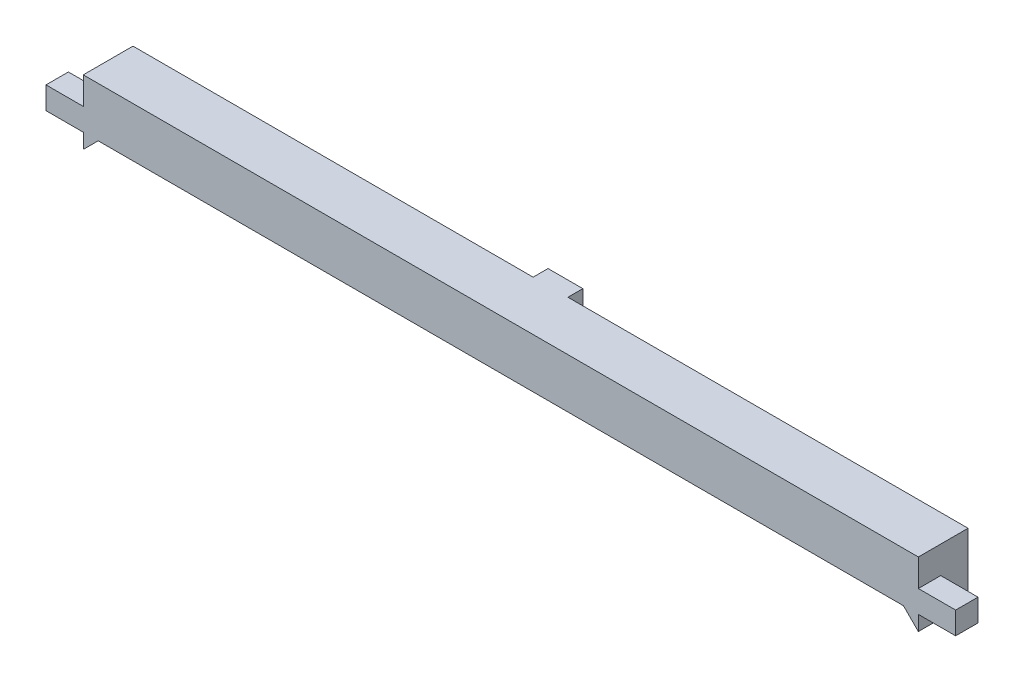
SolidWorks part; units mm, degrees
ref_plane "정면" through (0, 0, 0) normal (0, 0, 1) x (1, 0, 0)
ref_plane "윗면" through (0, 0, 0) normal (0, 1, 0) x (1, 0, 0)
ref_plane "우측면" through (0, 0, 0) normal (1, 0, 0) x (0, 0, -1)
sketch "스케치1" plane through (0, 0, 0) normal (0, 0, 1) x (1, 0, 0)
  line L0 (-318.5049, 0) -> (318.5049, 0) construction
  line L1 (0, 0) -> (0, -258.8265) construction
  line L2 (-168, 0) -> (168, 0)
  line L3 (-168, -20) -> (168, -20)
  line L4 (168, -20) -> (168, 0) construction
  line L5 (168, -20) -> (168, -340)
  line L6 (172, -340) -> (172, 0)
  line L7 (168, 0) -> (183, 0)
  line L8 (183, 0) -> (183, -340)
  line L9 (183, -340) -> (168, -340)
  line L10 (-168, -20) -> (-168, 0) construction
  line L11 (-183, -340) -> (-168, -340)
  line L12 (-183, 0) -> (-183, -340)
  line L13 (-168, 0) -> (-183, 0)
  line L14 (-172, -340) -> (-172, 0)
  line L15 (-168, -20) -> (-168, -340)
  line L16 (168, -20) -> (168, 0)
  line L17 (-168, -20) -> (-168, 0)
  point P14 (0, -20)
  dimension "D1" = 168
  dimension "D2" = 20
  dimension "D3" = 4
  dimension "D4" = 340
  dimension "D5" = 15
extrude "보스-돌출1" add sketch "스케치1" along normal blind 26 contours L3 L5 L9 L8 L7 L2 L13 L12 L11 L15
extrude "보스-돌출2" add sketch "스케치1<4>" against normal blind 19 contours L16 L5 L9 L6 L7 | L15 L17 L13 L14 L11 region at (-170, -170, 0) region at (170, -170, 0)
sketch "스케치1<4>" plane through (0, 0, 0) normal (0, 0, 1) x (1, 0, 0) same geometry as "스케치1"
fillet "필렛1" radius 10 4 edges at (-170, 0, -19) (170, 0, -19) (170, -340, -19) (-170, -340, -19)
sketch "스케치2" plane through (172, 0, 0) normal (1, 0, 0) x (0, 0, -1)
  line L0 (14, -340) -> (14, 0)
  line L1 (12, 0) -> (12, -340)
  line L4 (19, -330) -> (19, -10)
  line L5 (9, 0) -> (0, 0)
  line L6 (0, 0) -> (0, -340)
  line L7 (0, -340) -> (9, -340)
  line L8 (19, -330) -> (19, -10)
  line L9 (9, 0) -> (0, 0)
  line L10 (0, 0) -> (0, -340)
  line L11 (0, -340) -> (9, -340)
  arc A2 (19, -10) -> (9, 0) centre (9, -10) ccw
  arc A3 (9, -340) -> (19, -330) centre (9, -330) ccw
  arc A4 (19, -10) -> (9, 0) centre (9, -10) ccw
  arc A5 (9, -340) -> (19, -330) centre (9, -330) ccw
  dimension "D2" = 5
  dimension "D3" = 2
  dimension "D1" = 0
sketch "스케치3" plane through (168, 0, 0) normal (-1, 0, 0) x (0, 0, 1)
  line L0 (-12, 0) -> (-12, -340) construction
  line L1 (-14, -340) -> (-14, 0) construction
  line L2 (-12, 0) -> (-12, -340)
  line L3 (-14, -340) -> (-14, 0)
  line L4 (-19, -10) -> (-19, -330)
  line L5 (0, 0) -> (-9, 0)
  line L6 (0, -340) -> (0, 0)
  line L7 (-9, -340) -> (0, -340)
  line L8 (-19, -10) -> (-19, -330)
  line L9 (0, 0) -> (-9, 0)
  line L10 (0, -340) -> (0, 0)
  line L11 (-9, -340) -> (0, -340)
  arc A2 (-9, 0) -> (-19, -10) centre (-9, -10) ccw
  arc A3 (-19, -330) -> (-9, -340) centre (-9, -330) ccw
  arc A4 (-9, 0) -> (-19, -10) centre (-9, -10) ccw
  arc A5 (-19, -330) -> (-9, -340) centre (-9, -330) ccw
  arc M8 (-9, 0) -> (-19, -10) centre (-9, -10) ccw
  arc M10 (-19, -330) -> (-9, -340) centre (-9, -330) ccw
  dimension "D1" = 0
extrude "보스-돌출3" add sketch "스케치3" along normal blind 2 contours L3 L2 M10 M8 region at (168, -170, -12.9991)
mirror "대칭 복사1" about plane through (0, 0, 0) normal (1, 0, 0) of "보스-돌출3"
sketch "스케치5" plane through (0, 0, 0) normal (0, 1, 0) x (1, 0, 0)
  line L0 (-7, 0) -> (-7, -26)
  line L1 (7, 0) -> (7, -26)
  line L2 (-168, 0) -> (-168, -6)
  line L3 (-168, -6) -> (-7, -6)
  line L4 (7, -6) -> (168, -6)
  line L5 (168, -6) -> (168, 0)
  line L12 (-168, 0) -> (-168, 9)
  line L13 (-168, 9) -> (-172, 9)
  line L14 (-172, 9) -> (-172, 0)
  line L15 (-172, 0) -> (-183, 0)
  line L16 (-183, 0) -> (-183, -26)
  line L17 (-183, -26) -> (183, -26)
  line L18 (183, -26) -> (183, 0)
  line L19 (183, 0) -> (172, 0)
  line L20 (172, 0) -> (172, 9)
  line L21 (172, 9) -> (168, 9)
  line L22 (168, 9) -> (168, 0)
  line L23 (168, 0) -> (-168, 0)
  line L24 (-168, 0) -> (-168, 9)
  line L25 (-168, 9) -> (-172, 9)
  line L26 (-172, 9) -> (-172, 0)
  line L27 (-172, 0) -> (-183, 0)
  line L28 (-183, 0) -> (-183, -26)
  line L29 (-183, -26) -> (183, -26)
  line L30 (183, -26) -> (183, 0)
  line L31 (183, 0) -> (172, 0)
  line L32 (172, 0) -> (172, 9)
  line L33 (172, 9) -> (168, 9)
  line L34 (168, 9) -> (168, 0)
  line L35 (168, 0) -> (-168, 0)
  line M27 (168, 0) -> (-168, 0)
  dimension "D2" = 7
  dimension "D3" = 7
  dimension "D4" = 6
  dimension "D1" = 0
extrude "컷-돌출1" cut sketch "스케치5" against normal blind 52 contours L2 L3 L0 M27 | L4 L5 L1 M27 region at (-87.5, 0, 3) region at (87.5, 0, 3)
sketch "스케치7" plane through (168, 0, 0) normal (-1, 0, 0) x (0, 0, 1)
  line L0 (26, 0) -> (6, 0)
  line L1 (-9, 0) -> (6, 0)
  line L2 (-14, -338.6603) -> (-14, -1.3397)
  line L3 (-19, -10) -> (-19, -330)
  line L4 (-14, -338.6603) -> (-14, -1.3397)
  line L5 (-19, -10) -> (-19, -330)
  line L6 (26, -20) -> (6, -20)
  line L7 (6, -20) -> (6, 0)
  line L8 (6, 0) -> (-9, 0)
  line L9 (-12, -0.4606) -> (-12, -339.5394)
  line L10 (-9, -340) -> (26, -340)
  line L11 (26, -340) -> (26, -20)
  line L12 (26, -20) -> (6, -20)
  line L13 (6, -20) -> (6, 0)
  line L14 (6, 0) -> (-9, 0)
  line L15 (-12, -0.4606) -> (-12, -339.5394)
  line L16 (-9, -340) -> (26, -340)
  line L17 (26, -340) -> (26, -20)
  line L18 (-9, 0) -> (6, 0)
  line L19 (26, 0) -> (6, 0)
  line L20 (26, -20) -> (26, -340)
  line L21 (26, -20) -> (26, 0)
  line L22 (26, -20) -> (26, 0)
  line L23 (26, -20) -> (26, -340)
  arc A1 (-19, -330) -> (-14, -338.6603) centre (-9, -330) ccw
  arc A2 (-9, 0) -> (-12, -0.4606) centre (-9, -10) ccw
  arc A3 (-12, -339.5394) -> (-9, -340) centre (-9, -330) ccw
  arc A4 (-9, 0) -> (-12, -0.4606) centre (-9, -10) ccw
  arc A5 (-12, -339.5394) -> (-9, -340) centre (-9, -330) ccw
  arc A6 (-19, -330) -> (-14, -338.6603) centre (-9, -330) ccw
  arc A7 (-14, -1.3397) -> (-19, -10) centre (-9, -10) ccw
  arc A8 (-19, -330) -> (-14, -338.6603) centre (-9, -330) ccw
  arc A9 (-14, -1.3397) -> (-19, -10) centre (-9, -10) ccw
  arc A10 (-14, -338.6603) -> (-12, -339.5394) centre (-9, -330) ccw
  arc A11 (-12, -339.5394) -> (-9, -340) centre (-9, -330) ccw
  arc A12 (-12, -339.5394) -> (-9, -340) centre (-9, -330) ccw
  arc A13 (-14, -338.6603) -> (-12, -339.5394) centre (-9, -330) ccw
  arc A14 (-19, -330) -> (-14, -338.6603) centre (-9, -330) ccw
  arc A15 (-9, 0) -> (-12, -0.4606) centre (-9, -10) ccw
  arc A16 (-12, -0.4606) -> (-14, -1.3397) centre (-9, -10) ccw
  arc A17 (-14, -1.3397) -> (-19, -10) centre (-9, -10) ccw
  arc A18 (-14, -1.3397) -> (-19, -10) centre (-9, -10) ccw
  arc A19 (-12, -0.4606) -> (-14, -1.3397) centre (-9, -10) ccw
  arc A20 (-9, 0) -> (-12, -0.4606) centre (-9, -10) ccw
  line M13 (26, -20) -> (6, -20)
  line M14 (6, -20) -> (6, 0)
  line M15 (6, 0) -> (-9, 0)
  arc M16 (-9, 0) -> (-12, -0.4606) centre (-9, -10) ccw
  line M17 (-12, -0.4606) -> (-12, -339.5394)
  arc M18 (-12, -339.5394) -> (-9, -340) centre (-9, -330) ccw
  line M19 (-9, -340) -> (26, -340)
  line M20 (26, -340) -> (26, -20)
  dimension "D1" = 0
  dimension "D2" = 0
extrude "컷-돌출2" cut sketch "스케치7" against normal blind 72 contours M20 M13 M14 M15 M16 M17 M18 M19 | L4 A9 L5 A8 | A19 L4 A13 M17 | L22 L19 M13 M14 region at (168, -10, 16) region at (168, -175.1122, 6.7138) region at (168, -170, -12.9991) region at (168, -170, -16.4834)
sketch "스케치8" plane through (-168, 0, 0) normal (1, 0, 0) x (0, 0, -1)
  line L6 (-6, 0) -> (-6, -20)
  line L7 (-6, -20) -> (-26, -20)
  line L8 (-26, -20) -> (-26, -340)
  line L9 (-26, -340) -> (9, -340)
  line L10 (12, -339.5394) -> (12, -0.4606)
  line L11 (9, 0) -> (-6, 0)
  line L12 (-6, 0) -> (-6, -20)
  line L13 (-6, -20) -> (-26, -20)
  line L14 (-26, -20) -> (-26, -340)
  line L15 (-26, -340) -> (9, -340)
  line L16 (12, -339.5394) -> (12, -0.4606)
  line L17 (9, 0) -> (-6, 0)
  line L18 (9, 0) -> (-6, 0)
  line L19 (-6, 0) -> (-26, 0)
  line L20 (-6, 0) -> (-26, 0)
  line L21 (9, 0) -> (-6, 0)
  line L22 (-26, 0) -> (-26, -20)
  line L23 (-26, -20) -> (-26, -340)
  line L24 (-26, -20) -> (-26, -340)
  line L25 (-26, 0) -> (-26, -20)
  arc A2 (9, -340) -> (12, -339.5394) centre (9, -330) ccw
  arc A3 (12, -0.4606) -> (9, 0) centre (9, -10) ccw
  arc A4 (9, -340) -> (12, -339.5394) centre (9, -330) ccw
  arc A5 (12, -0.4606) -> (9, 0) centre (9, -10) ccw
  line M9 (-6, 0) -> (-6, -20)
  line M10 (-6, -20) -> (-26, -20)
  line M11 (-26, -20) -> (-26, -340)
  line M12 (-26, -340) -> (9, -340)
  arc M13 (9, -340) -> (12, -339.5394) centre (9, -330) ccw
  line M14 (12, -339.5394) -> (12, -0.4606)
  arc M15 (12, -0.4606) -> (9, 0) centre (9, -10) ccw
  line M16 (9, 0) -> (-6, 0)
  dimension "D1" = 0
extrude "컷-돌출3" cut sketch "스케치8" against normal blind 72 contours M16 M9 M10 M11 M12 M13 M14 M15 | L20 L25 M10 M9 region at (-168, -175.1122, 6.7138) region at (-168, -10, 16)
extrude "컷-돌출4" cut sketch "스케치7<3>" along normal blind 362 contours L4 A9 L5 A8 | A19 L4 A13 M17 region at (168, -170, -12.9991) region at (168, -170, -16.4834)
sketch "스케치7<3>" plane through (168, 0, 0) normal (-1, 0, 0) x (0, 0, 1) same geometry as "스케치7"
sketch "스케치9" plane through (168, 0, 0) normal (1, 0, 0) x (0, 0, -1)
  line L0 (9, -340) -> (-26, -340) construction
  line L1 (-26, -340) -> (-26, -20) construction
  line L2 (-26, -20) -> (-26, -340) construction
  line L3 (12, -0.4606) -> (12, -339.5394) construction
  line L4 (-6, -20) -> (-6, 0)
  line L5 (-6, 0) -> (-26, 0)
  line L6 (-26, 0) -> (-26, -20)
  line L7 (-26, -20) -> (-6, -20)
  line L8 (-6, -20) -> (-6, 0)
  line L9 (-6, 0) -> (-26, 0)
  line L10 (-26, 0) -> (-26, -20)
  line L11 (-26, -20) -> (-6, -20)
  line L12 (-6, 0) -> (9, 0) construction
  line L13 (9, 0) -> (-6, 0) construction
  line L14 (-26, -20) -> (-6, -20) construction
  line L15 (-6, -20) -> (-6, 0) construction
  line L16 (-26, 0) -> (-6, 0) construction
  line L17 (-26, -20) -> (-26, 0) construction
  line L18 (19, -10) -> (19, -330) construction
  line L19 (14, -338.6603) -> (14, -1.3397) construction
  line L20 (9, -340) -> (-26, -340)
  line L21 (-26, -340) -> (-26, -20)
  line L22 (-26, -20) -> (-26, -340)
  line L23 (12, -0.4606) -> (12, -339.5394)
  line L24 (-6, 0) -> (9, 0)
  line L25 (9, 0) -> (-6, 0)
  line L26 (-26, -20) -> (-6, -20)
  line L27 (-6, -20) -> (-6, 0)
  line L28 (-26, 0) -> (-6, 0)
  line L29 (-26, -20) -> (-26, 0)
  line L30 (19, -10) -> (19, -330)
  line L31 (14, -338.6603) -> (14, -1.3397)
  line L32 (-26, -10) -> (-16, -10)
  line L33 (-16, -10) -> (-16, -20)
  line L34 (-26, -11) -> (-17, -11)
  line L35 (-17, -11) -> (-17, -20)
  arc A0 (9, -340) -> (12, -339.5394) centre (9, -330) ccw construction
  arc A1 (9, -340) -> (12, -339.5394) centre (9, -330) ccw construction
  arc A2 (12, -339.5394) -> (14, -338.6603) centre (9, -330) ccw construction
  arc A3 (12, -0.4606) -> (9, 0) centre (9, -10) ccw construction
  arc A4 (14, -1.3397) -> (12, -0.4606) centre (9, -10) ccw construction
  arc A5 (12, -0.4606) -> (9, 0) centre (9, -10) ccw construction
  arc A6 (14, -338.6603) -> (19, -330) centre (9, -330) ccw construction
  arc A7 (14, -338.6603) -> (19, -330) centre (9, -330) ccw construction
  arc A8 (19, -10) -> (14, -1.3397) centre (9, -10) ccw construction
  arc A9 (19, -10) -> (14, -1.3397) centre (9, -10) ccw construction
  arc A10 (9, -340) -> (12, -339.5394) centre (9, -330) ccw
  arc A11 (9, -340) -> (12, -339.5394) centre (9, -330) ccw
  arc A12 (12, -339.5394) -> (14, -338.6603) centre (9, -330) ccw
  arc A13 (12, -0.4606) -> (9, 0) centre (9, -10) ccw
  arc A14 (14, -1.3397) -> (12, -0.4606) centre (9, -10) ccw
  arc A15 (12, -0.4606) -> (9, 0) centre (9, -10) ccw
  arc A16 (14, -338.6603) -> (19, -330) centre (9, -330) ccw
  arc A17 (14, -338.6603) -> (19, -330) centre (9, -330) ccw
  arc A18 (19, -10) -> (14, -1.3397) centre (9, -10) ccw
  arc A19 (19, -10) -> (14, -1.3397) centre (9, -10) ccw
  line M9 (-26, 0) -> (-26, -20)
  line M10 (-26, -20) -> (-6, -20)
  dimension "D2" = 10
  dimension "D3" = 10
  dimension "D1" = 0
  dimension "D4" = 1
extrude "보스-돌출4" add sketch "스케치9" along normal blind 15 contours L35 L34 M9 M10 region at (168, -15.5, 21.5)
mirror "대칭 복사2" about plane through (0, 0, 0) normal (1, 0, 0) of "보스-돌출4"
sketch "스케치10" plane through (0, 0, 26) normal (0, 0, 1) x (1, 0, 0)
  line L8 (-168, 0) -> (-168, -11)
  line L9 (-168, -11) -> (-183, -11)
  line L10 (-183, -11) -> (-183, -20)
  line L11 (-183, -20) -> (183, -20)
  line L12 (183, -20) -> (183, -11)
  line L13 (183, -11) -> (168, -11)
  line L14 (168, -11) -> (168, 0)
  line L15 (168, 0) -> (-168, 0)
  line L16 (-168, 0) -> (-168, -11)
  line L17 (-168, -11) -> (-183, -11)
  line L18 (-183, -11) -> (-183, -20)
  line L19 (-183, -20) -> (183, -20)
  line L20 (183, -20) -> (183, -11)
  line L21 (183, -11) -> (168, -11)
  line L22 (168, -11) -> (168, 0)
  line L23 (168, 0) -> (-168, 0)
  line L24 (-183, -20) -> (183, -20)
  line L25 (-183, -20) -> (183, -20)
  line L26 (168, -11) -> (168, 0)
  line L27 (168, -11) -> (168, 0)
  line L28 (168, -11) -> (168, -36.4678) construction
  line L29 (168, -20) -> (168, -26)
  line L30 (168, -26) -> (162, -20)
  line L31 (0, 0) -> (0, -20) construction
  dimension "D2" = 6
  dimension "D3" = 6
  dimension "D1" = 0
extrude "보스-돌출5" add sketch "스케치10" against normal blind 20 contours L30 L29 L25 region at (166, -22, 26)
mirror "대칭 복사3" about plane through (0, 0, 0) normal (1, 0, 0) of "보스-돌출5"
sketch "스케치11" plane through (0, 0, 0) normal (0, 1, 0) x (1, 0, 0)
  line L0 (0, -26) -> (0, 64.4586) construction
  line L1 (168, -26) -> (-168, -26) construction
  line L2 (7, -6) -> (168, -6)
  line L3 (7, -6) -> (168, -6)
  line L4 (-168, -6) -> (-7, -6)
  line L5 (-168, -6) -> (-7, -6)
  line L6 (168, -26) -> (-168, -26)
  line L7 (168, -26) -> (-168, -26)
  line L8 (0, -26) -> (0, -21.153)
  line L9 (-1.1414, -20.1631) -> (-5.8586, -20.8369)
  line L10 (-7, -19.847) -> (-7, -14.153)
  line L11 (-5.8586, -13.1631) -> (-1.1414, -13.8369)
  line L12 (0, -12.847) -> (0, -7)
  line L13 (-7, 0) -> (-7, -6) construction
  line L14 (-7, -6) -> (-1, -6)
  line L15 (-168, -6) -> (-168, -26)
  line L16 (-168, -6) -> (-168, -26)
  line L17 (-0.5, -26) -> (-0.5, -21.153)
  line L18 (-1.0707, -20.658) -> (-5.7879, -21.3319)
  line L19 (-7.5, -19.847) -> (-7.5, -14.153)
  line L20 (-5.7879, -12.6681) -> (-1.0707, -13.342)
  line L21 (-168, -26) -> (-168, -17)
  line L22 (-168, -17) -> (-183, -17)
  line L23 (-183, -17) -> (-183, -26)
  line L24 (-183, -26) -> (-168, -26)
  line L25 (-168, -26) -> (-168, -17)
  line L26 (-168, -17) -> (-183, -17)
  line L27 (-183, -17) -> (-183, -26)
  line L28 (-183, -26) -> (-168, -26)
  line L29 (-0.5, -12.847) -> (-0.5, -7)
  line L30 (-7, -6.5) -> (-1, -6.5)
  line L31 (-7, -6.5) -> (-7, -6)
  line L32 (168, -6) -> (203.629, -6)
  line L33 (203.629, -6) -> (203.629, -26)
  line L34 (203.629, -26) -> (168, -26)
  line L35 (-7, 0) -> (7, 0)
  line L36 (-7, 0) -> (7, 0)
  line L37 (-7, 0) -> (-7, -6)
  line L38 (-7, 0) -> (-7, -6)
  line L39 (7, 0) -> (7, -6)
  line L40 (7, 0) -> (7, -6)
  line L41 (0, -21.153) -> (0, -12.847)
  arc A0 (0, -21.153) -> (-1.1414, -20.1631) centre (-1, -21.153) ccw
  arc A1 (-1.1414, -13.8369) -> (0, -12.847) centre (-1, -12.847) ccw
  arc A2 (-7, -14.153) -> (-5.8586, -13.1631) centre (-6, -14.153) cw
  arc A3 (-7, -19.847) -> (-5.8586, -20.8369) centre (-6, -19.847) ccw
  arc A4 (0, -7) -> (-1, -6) centre (-1, -7) ccw
  arc A5 (-0.5, -21.153) -> (-1.0707, -20.658) centre (-1, -21.153) ccw
  arc A6 (-7.5, -19.847) -> (-5.7879, -21.3319) centre (-6, -19.847) ccw
  arc A7 (-7.5, -14.153) -> (-5.7879, -12.6681) centre (-6, -14.153) cw
  arc A8 (-1.0707, -13.342) -> (-0.5, -12.847) centre (-1, -12.847) ccw
  arc A9 (-0.5, -7) -> (-1, -6.5) centre (-1, -7) ccw
  point P21 (0, -20)
  point P24 (0, -14)
  point P27 (-7, -13)
  point P30 (-7, -21)
  dimension "D5" = 1
  dimension "D6" = 1
  dimension "D1" = 1
  dimension "D2" = 6
  dimension "D3" = 1
  dimension "D4" = 1
  dimension "D7" = 6.847
  dimension "D10" = 35.629
  dimension "D8" = 0
  dimension "D9" = 0.5
